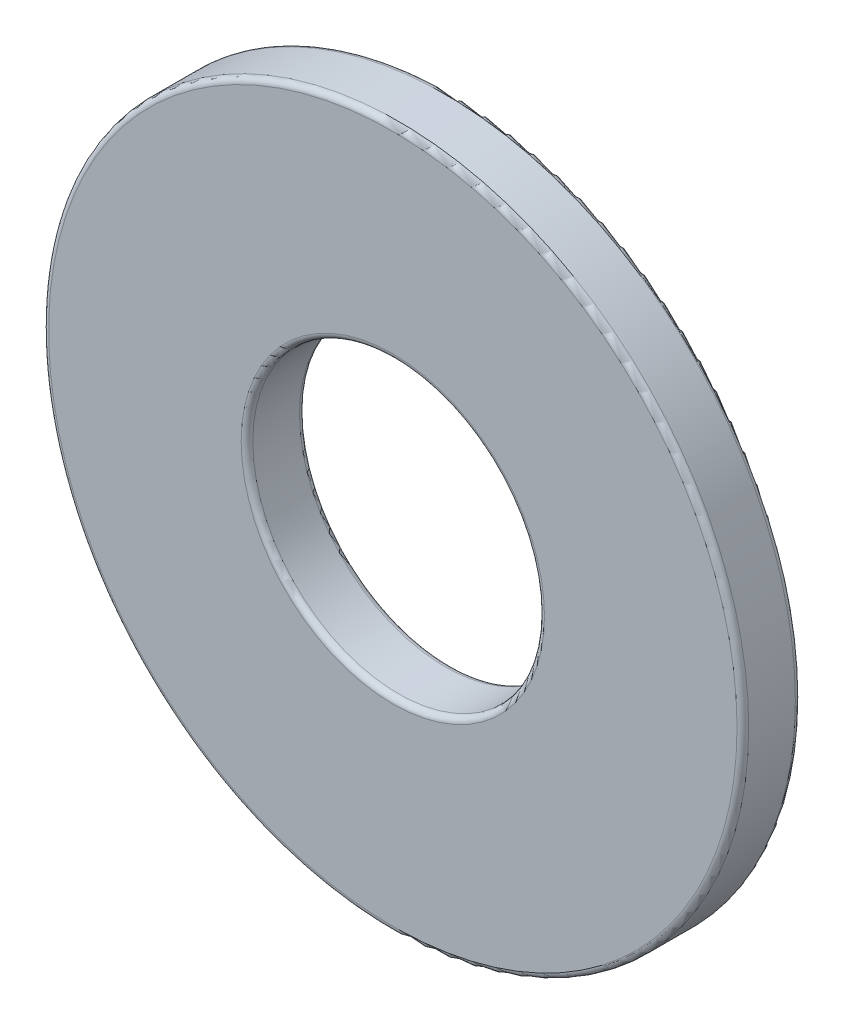
SolidWorks part; units mm, degrees
ref_plane "Front Plane" through (0, 0, 0) normal (0, 0, 1) x (1, 0, 0)
ref_plane "Top Plane" through (0, 0, 0) normal (0, 1, 0) x (1, 0, 0)
ref_plane "Right Plane" through (0, 0, 0) normal (1, 0, 0) x (0, 0, -1)
sketch "Sketch1" plane through (0, 0, 0) normal (0, 0, 1) x (1, 0, 0)
  line L0 (-19.05, 0) -> (-7.9375, 0) construction
  line L1 (-7.9375, 0) -> (7.9375, 0) construction
  line L2 (7.9375, 0) -> (19.05, 0) construction
  line L3 (0, 19.05) -> (0, -19.05) construction
  circle A0 centre (0, 0) radius 7.9375 construction
  circle A1 centre (0, 0) radius 19.05 construction
  point P11 (7.9375, 0)
  point P12 (-7.9375, 0)
  dimension "ID" = 15.875
  dimension "OD" = 38.1
sketch "Sketch2" plane through (0, 0, 0) normal (1, 0, 0) x (0, 0, -1)
  line L1 (-1.5875, -19.05) -> (1.5875, -19.05) construction
  line L2 (-1.5875, -19.05) -> (-1.5875, 19.05) construction
  line L3 (-1.5875, 19.05) -> (1.5875, 19.05) construction
  line L4 (1.5875, -19.05) -> (1.5875, 19.05) construction
  line L5 (-1.5875, -19.05) -> (1.5875, 19.05) construction
  line L6 (-1.5875, 19.05) -> (1.5875, -19.05) construction
  point P0 (0, 0)
  dimension "Thickness" = 3.175
sketch "Sketch3" plane through (0, 0, 0) normal (0, 0, 1) x (1, 0, 0)
  circle A0 centre (0, 0) radius 7.9375 construction
  circle A1 centre (0, 0) radius 19.05 construction
  circle A2 centre (0, 0) radius 7.9375
  circle A3 centre (0, 0) radius 19.05
extrude "Boss-Extrude1" add sketch "Sketch3" along normal up to vertex (1.5875 mm away) and the other way up to vertex (1.5875 mm away) up to point (0, 19.05, 1.5875) other way up to point (0, 19.05, -1.5875)
fillet "Fillet1" radius 0.3175 4 edges at (19.05, 0, -1.5875) (7.9375, 0, -1.5875) (7.9375, 0, 1.5875) (19.05, 0, 1.5875)
equation "\"D1@Fillet1\"=\"Thickness@Sketch2\"*.1"
